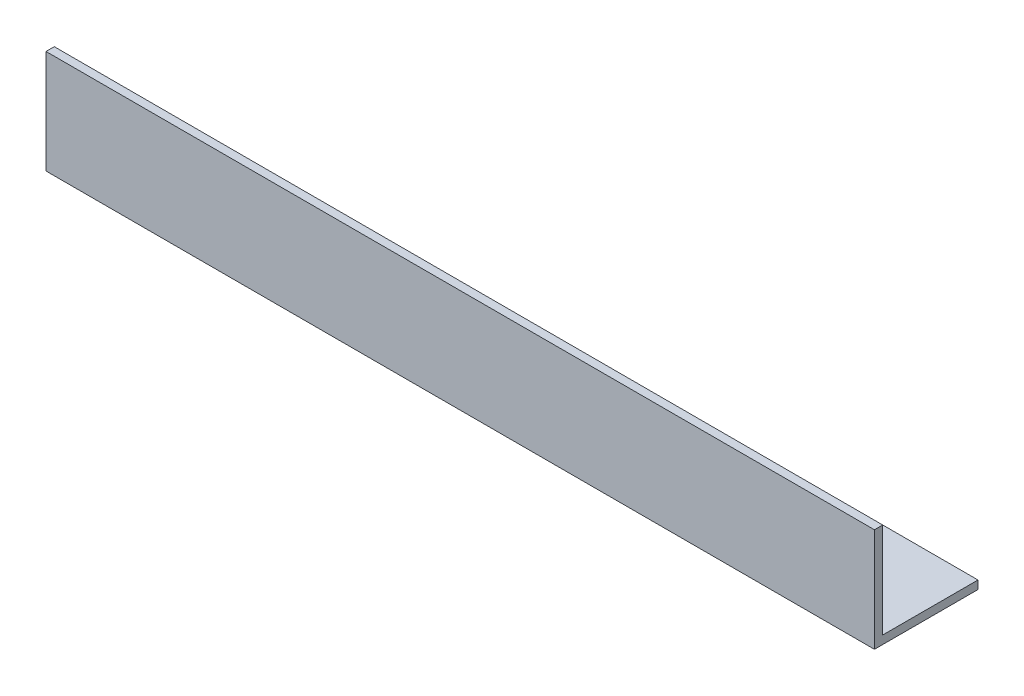
SolidWorks part; units mm, degrees
ref_plane "Спереди" through (0, 0, 0) normal (0, 0, 1) x (1, 0, 0)
ref_plane "Сверху" through (0, 0, 0) normal (0, 1, 0) x (1, 0, 0)
ref_plane "Справа" through (0, 0, 0) normal (1, 0, 0) x (0, 0, -1)
sketch "Эскиз1" plane through (0, 0, 0) normal (1, 0, 0) x (0, 0, -1)
  line L0 (0, 25) -> (0, 0)
  line L1 (0, 0) -> (25, 0)
extrude "Вытянуть-Тонкостенный1" add sketch "Эскиз1" along normal blind 200 thin thin type one direction reverse wall 2
